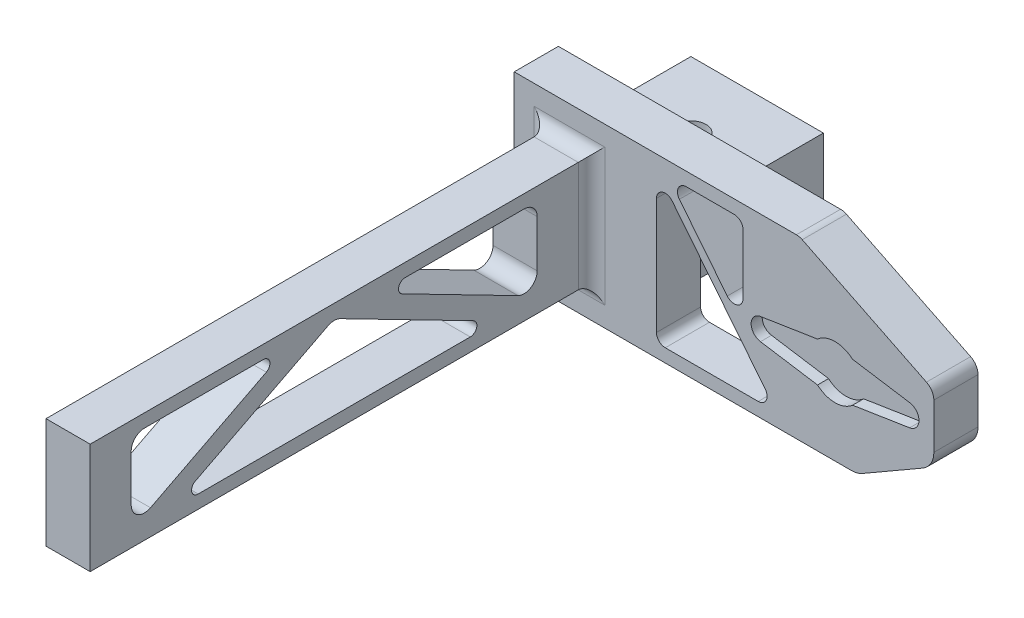
SolidWorks part; units mm, degrees
material "PLA"
ref_plane "Front Plane" through (0, 0, 0) normal (0, 0, 1) x (1, 0, 0)
ref_plane "Top Plane" through (0, 0, 0) normal (0, 1, 0) x (1, 0, 0)
ref_plane "Right Plane" through (0, 0, 0) normal (1, 0, 0) x (0, 0, -1)
sketch "Sketch3" plane through (0, 0, 0) normal (0, 0, 1) x (1, 0, 0)
  line L1 (-22.6388, -7.4411) -> (22.3612, -7.4411)
  line L2 (-22.6388, -7.4411) -> (-22.6388, 7.5589)
  line L3 (-22.6388, 7.5589) -> (22.3612, 7.5589)
  line L4 (22.3612, -7.4411) -> (22.3612, 7.5589)
  dimension "D1" = 15
  dimension "D2" = 45
extrude "Boss-Extrude1" add sketch "Sketch3" against normal blind 10
sketch "Sketch2" plane through (0, 0, 0) normal (0, 0, 1) x (1, 0, 0)
  line L0 (-16.8881, 2.4697) -> (-3.9686, 4.5)
  line L1 (-16.8881, -2.4697) -> (-3.9686, -4.5)
  line L2 (3.9686, 4.5) -> (16.8881, 2.4697)
  line L3 (16.8881, -2.4697) -> (3.9686, -4.5)
  arc A0 (-16.8881, 2.4697) -> (-16.8881, -2.4697) centre (-16.5, 0) ccw
  arc A1 (-3.9686, 4.5) -> (3.9686, 4.5) centre (0, 0) cw
  arc A2 (-3.9686, -4.5) -> (3.9686, -4.5) centre (0, 0) ccw
  arc A3 (16.8881, -2.4697) -> (16.8881, 2.4697) centre (16.5, 0) ccw
extrude "Cut-Extrude1" cut sketch "Sketch2" against normal blind 2.5
sketch "Sketch11" plane through (0, -7.4411, 0) normal (0, -1, 0) x (1, 0, 0)
  line L0 (8.25, 0) -> (-8.25, 0) construction
  line L1 (22.3612, -10) -> (-22.6388, -10)
  line L2 (22.3612, -10) -> (22.3612, 0)
  line L3 (22.3612, 0) -> (-22.6388, 0)
  line L4 (-22.6388, -10) -> (-22.6388, 0)
  line L5 (-22.6388, -10) -> (-22.6388, 0) construction
extrude "Boss-Extrude5" add sketch "Sketch11" along normal blind 10
sketch "Sketch14" plane through (0, 7.5589, 0) normal (0, 1, 0) x (1, 0, 0)
  line L0 (-8.25, 0) -> (8.25, 0) construction
  line L1 (22.3612, 10) -> (-22.6388, 10)
  line L2 (22.3612, 10) -> (22.3612, 0)
  line L3 (22.3612, 0) -> (-22.6388, 0)
  line L4 (-22.6388, 10) -> (-22.6388, 0)
  line L5 (-22.6388, 10) -> (-22.6388, 0) construction
extrude "Boss-Extrude7" add sketch "Sketch14" along normal blind 15
sketch "Sketch20" plane through (-22.6388, 0, 0) normal (-1, 0, 0) x (0, 0, 1)
  line L0 (0, -22) -> (0, 22) construction
  line L1 (-10, 22.5589) -> (0, 22.5589)
  line L2 (-10, 22.5589) -> (-10, -17.4411)
  line L3 (-10, -17.4411) -> (0, -17.4411)
  line L4 (0, 22.5589) -> (0, -17.4411)
  line L5 (0, -17.4411) -> (-10, -17.4411) construction
extrude "Boss-Extrude10" add sketch "Sketch20" along normal blind 50
sketch "Sketch21" plane through (0, 0, 0) normal (0, 0, 1) x (1, 0, 0)
  line L1 (-65.1388, 15.0589) -> (-55.1388, 15.0589)
  line L2 (-65.1388, 15.0589) -> (-65.1388, -9.9411)
  line L3 (-65.1388, -9.9411) -> (-55.1388, -9.9411)
  line L4 (-55.1388, 15.0589) -> (-55.1388, -9.9411)
  line L5 (-72.6388, 22.5589) -> (22.3612, 22.5589) construction
  line L6 (-72.6388, -17.4411) -> (-72.6388, 22.5589) construction
  dimension "D1" = 7.5
  dimension "D2" = 25
  dimension "D3" = 7.5
  dimension "D4" = 10
extrude "Boss-Extrude11" add sketch "Sketch21" along normal blind 113.5
sketch "Sketch22" plane through (0, 0, -10) normal (0, 0, -1) x (-1, 0, 0)
  line L0 (72.6388, 22.5589) -> (72.6388, -17.4411) construction
  line L1 (42.6388, 5.5589) -> (72.6388, 5.5589)
  line L2 (42.6388, 5.5589) -> (42.6388, -0.4411)
  line L3 (42.6388, -0.4411) -> (72.6388, -0.4411)
  line L4 (72.6388, 5.5589) -> (72.6388, -0.4411)
  line L5 (42.6388, 5.5589) -> (72.6388, -0.4411) construction
  line L6 (42.6388, -0.4411) -> (72.6388, 5.5589) construction
  line L7 (72.6388, -17.4411) -> (-22.3612, -17.4411) construction
  point P0 (57.6388, 2.5589)
  dimension "D1" = 20
  dimension "D2" = 30
  dimension "D3" = 6
extrude "Boss-Extrude12" add sketch "Sketch22" along normal blind 30
sketch "Sketch23" plane through (0, -0.4411, 0) normal (0, -1, 0) x (1, 0, 0)
  line L1 (-72.6388, -10) -> (-42.6388, -10)
  line L2 (-72.6388, -10) -> (-72.6388, -40)
  line L3 (-72.6388, -40) -> (-42.6388, -40)
  line L4 (-42.6388, -10) -> (-42.6388, -40)
extrude "Boss-Extrude13" add sketch "Sketch23" along normal blind 8.5
fillet "Fillet1" radius 3 4 edges at (-60.1388, 15.0589, 0) (-65.1388, 2.5589, 0) (-55.1388, 2.5589, 0) (-60.1388, -9.9411, 0)
chamfer "Chamfer1" distance 15 angle 63.75 1 edges at (22.3612, 22.5589, -5) first distance on face at (22.3612, 2.5589, -5)
fillet "Fillet2" radius 3 2 edges at (-8.0558, 22.5589, -5) (22.3612, 7.5589, -5)
chamfer "Chamfer2" distance 10 angle 60 1 edges at (22.3612, -17.4411, -5) first distance on face at (22.3612, -5.8739, -5)
fillet "Fillet3" radius 5 2 edges at (5.0406, -17.4411, -5) (22.3612, -7.4411, -5)
sketch "Sketch24" plane through (-65.1388, 0, 0) normal (-1, 0, 0) x (0, 0, 1)
  line L0 (58.25, 15.0589) -> (58.25, -9.9411) construction
  line L1 (113.5, 15.0589) -> (3, 15.0589) construction
  line L2 (113.5, -9.9411) -> (3, -9.9411) construction
  line L3 (58.25, -6.9411) -> (95.25, -6.9411)
  line L4 (58.25, -6.9411) -> (21.25, -6.9411)
  line L5 (21.25, -6.9411) -> (58.25, 12.0589)
  line L6 (58.25, 12.0589) -> (95.25, -6.9411)
  line L7 (48.399, 12.0589) -> (12.29, -6.4835)
  line L8 (48.399, 12.0589) -> (12.29, 12.0589)
  line L9 (12.29, 12.0589) -> (12.29, -6.4835)
  line L10 (68.101, 12.0589) -> (104.21, 12.0589)
  line L11 (68.101, 12.0589) -> (104.21, -6.4835)
  line L12 (104.21, 12.0589) -> (104.21, -6.4835)
  dimension "D1" = 37
  dimension "D2" = 37
  dimension "D3" = 3
  dimension "D4" = 3
  dimension "D5" = 3
  dimension "D6" = 4.5
  dimension "D7" = 18.5424
extrude "Cut-Extrude2" cut sketch "Sketch24" against normal through all
fillet "Fillet4" radius 3 5 edges at (-60.1388, -6.4835, 12.29) (-60.1388, 12.0589, 12.29) (-60.1388, -6.4835, 104.21) (-60.1388, 12.0589, 104.21) (-60.1388, 12.0589, 58.25)
fillet "Fillet5" radius 1.5 4 edges at (-60.1388, 12.0589, 68.101) (-60.1388, -6.9411, 95.25) (-60.1388, -6.9411, 21.25) (-60.1388, 12.0589, 48.399)
sketch "Sketch25" plane through (0, 0, -10) normal (0, 0, -1) x (-1, 0, 0)
  line L0 (40.4388, 19.5589) -> (13.2313, -14.4411)
  line L1 (13.2313, -14.4411) -> (40.4388, -14.4411)
  line L2 (40.4388, -14.4411) -> (40.4388, 19.5589)
  line L3 (72.6388, -17.4411) -> (-3.7009, -17.4411) construction
  line L5 (8.7553, 22.5589) -> (72.6388, 22.5589) construction
  line L6 (42.6388, 5.5589) -> (42.6388, -8.9411) construction
  dimension "D1" = 3
  dimension "D2" = 3
  dimension "D3" = 2.2
extrude "Cut-Extrude3" cut sketch "Sketch25" against normal through all
sketch "Sketch26" plane through (0, 0, 0) normal (0, 0, 1) x (1, 0, 0)
  line L0 (-20.8402, -1.7311) -> (-20.8402, 19.513)
  line L1 (-20.8402, 19.513) -> (-37.8402, 19.513)
  line L2 (-37.8402, 19.513) -> (-20.8402, -1.7311)
  line L3 (-40.4388, 19.5589) -> (-13.2313, -14.4411) construction
  dimension "D1" = 2.0003
  dimension "D2" = 17
extrude "Cut-Extrude4" cut sketch "Sketch26" against normal through all
fillet "Fillet6" radius 2 6 edges at (-13.2313, -14.4411, -5) (-40.4388, -14.4411, -5) (-40.4388, 19.5589, -5) (-20.8402, -1.7311, -5) (-20.8402, 19.513, -5) (-37.8402, 19.513, -5)
sketch "Sketch30" plane through (0, 5.5589, 0) normal (0, 1, 0) x (1, 0, 0)
  line L0 (-72.6388, 40) -> (-42.6388, 10) construction
  line L1 (-42.6388, 40) -> (-72.6388, 10) construction
  point P10 (-57.6388, 25)
hole_wizard "M8 Tapped Hole1" positions "Sketch30" profile "Sketch31" tap size "M8" standard "ISO"
sketch "Sketch31" plane through (-57.6388, 5.5589, -25) normal (1, 0, 0) x (0, 0, 1)
  line L0 (0, 0) -> (0, 24.2929)
  line L1 (0, 24.2929) -> (3.4, 22.25)
  line L2 (3.4, 22.25) -> (3.4, 0)
  line L5 (3.4, 0) -> (0, 0)
  line L10 (0, 24.2929) -> (-3.4, 22.25) construction
  line L11 (0, -6.35) -> (0, 107.95) construction
  dimension "Tap Drill Dia." = 6.8
  dimension "Tap Drill Depth" = 22.25
  dimension "Drill Angle" = 118
cosmetic thread "Hole Thread1" parameters "D1"=16, "D2"=8
